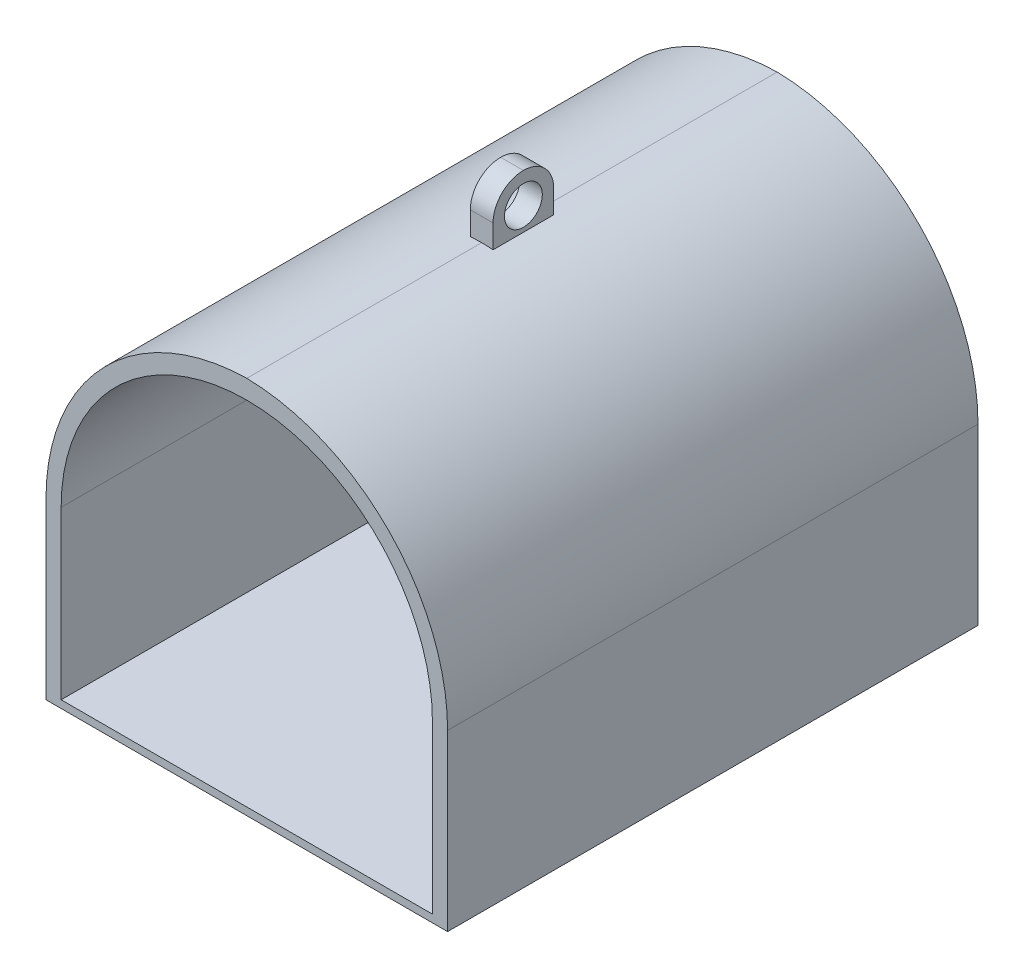
SolidWorks part; units mm, degrees
ref_plane "Plan de face" through (0, 0, 0) normal (0, 0, 1) x (1, 0, 0)
ref_plane "Plan de dessus" through (0, 0, 0) normal (0, 1, 0) x (1, 0, 0)
ref_plane "Plan de droite" through (0, 0, 0) normal (1, 0, 0) x (0, 0, -1)
sketch "Esquisse1" plane through (0, 0, 0) normal (0, 0, 1) x (1, 0, 0)
  line L1 (0, 0) -> (53, 0)
  line L2 (0, 0) -> (0, 50)
  line L3 (0, 50) -> (53, 50)
  line L4 (53, 0) -> (53, 50)
  point P1 (0, 50)
  point P2 (0.4556, 50)
  point P8 (50, 50)
  point P9 (0, 50)
  point P10 (50, 49.5793)
  dimension "D1" = 50
  dimension "D2" = 53
extrude "Boss.-Extru.1" add sketch "Esquisse1" along normal blind 70
sketch "Esquisse5" plane through (0, 50, 0) normal (0, 1, 0) x (1, 0, 0)
  line L0 (0, -70) -> (0, 0) construction
  line L1 (25, -39) -> (28, -39)
  line L2 (25, -39) -> (25, -31)
  line L3 (25, -31) -> (28, -31)
  line L4 (28, -39) -> (28, -31)
  line L5 (25, -39) -> (28, -31) construction
  line L6 (25, -31) -> (28, -39) construction
  line L7 (53, -70) -> (53, 0) construction
  point P0 (26.5, -35)
  dimension "D1" = 3
  dimension "D2" = 26.5
  dimension "D3" = 26.5
  dimension "D4" = 8
extrude "Boss.-Extru.2" add sketch "Esquisse5" along normal blind 7
fillet "Congé1" radius 4 2 edges at (26.5, 57, 31) (26.5, 57, 39)
fillet "Congé2" radius 27 2 edges at (0, 50, 35) (53, 50, 35)
sketch "Esquisse8" plane through (25, 0, 0) normal (-1, 0, 0) x (0, 0, 1)
  circle A0 centre (35, 53) radius 2.5
  dimension "D1" = 5
extrude "Enlèv. mat.-Extru.3" cut sketch "Esquisse8" against normal blind 7
sketch "Esquisse9" plane through (0, 0, 70) normal (0, 0, 1) x (1, 0, 0)
  line L1 (2, 1) -> (51, 1)
  line L2 (2, 1) -> (2, 23)
  line L4 (51, 1) -> (51, 23)
  line L5 (53, 0) -> (53, 23) construction
  line L6 (0, 0) -> (53, 0) construction
  line L8 (0, 23) -> (0, 0) construction
  arc A0 (26.5162, 47.5) -> (51, 23) centre (26.5, 23) cw
  arc A1 (2, 23) -> (26.5162, 47.5) centre (26.5, 23) cw
  point P7 (26.0879, 47.9363)
  point P8 (27.0611, 44.0903)
  point P15 (26.4755, 48.4619)
  point P16 (0, 0)
  point P17 (0, 0)
  point P18 (0, 0)
  dimension "D1" = 1
  dimension "D5" = 24.5
  dimension "D6" = 49
  dimension "D2" = 2
  dimension "D3" = 2
  dimension "D4" = 22
extrude "Enlèv. mat.-Extru.4" cut sketch "Esquisse9" against normal blind 68
